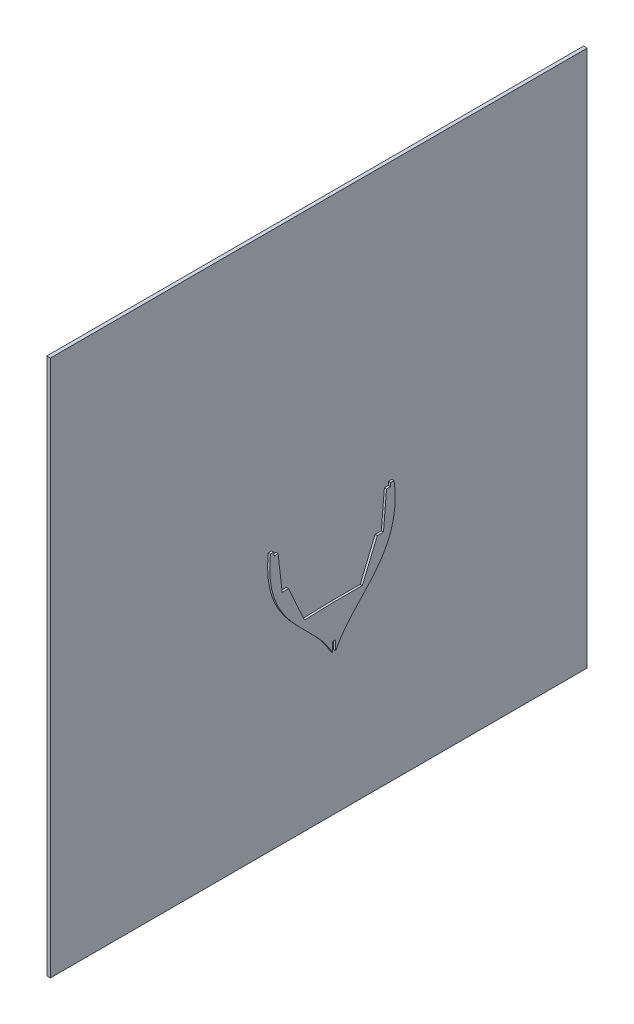
SolidWorks part; units mm, degrees
ref_plane "Plan de face" through (0, 0, 0) normal (0, 0, 1) x (1, 0, 0)
ref_plane "Plan de dessus" through (0, 0, 0) normal (0, 1, 0) x (1, 0, 0)
ref_plane "Plan de droite" through (0, 0, 0) normal (1, 0, 0) x (0, 0, -1)
sketch "Esquisse1" plane through (0, 0, 0) normal (0, 0, 1) x (1, 0, 0)
  point P0 (-20, 0)
  dimension "D1" = 20
sketch3d "Esquisse3D1"
  line L1 (-20, 1121.2893, 777.275) -> (-20, 1121.2893, -722.725)
  line L2 (-20, 1121.2893, 777.275) -> (-20, -378.7107, 777.275)
  line L3 (-20, -378.7107, 777.275) -> (-20, -378.7107, -722.725)
  line L4 (-20, 1121.2893, -722.725) -> (-20, -378.7107, -722.725)
  dimension "D1" = 1500
  dimension "D2" = 1500
extrude "Boss.-Extru.2" add sketch "Esquisse3D1" along direction (1, 0, 0) on the side of the normal blind 10 contours L2 L1 L4 L3
sketch "Esquisse2" plane through (0, 0, 0) normal (1, 0, 0) x (0, 0, -1)
  line L0 (0, 0) -> (-6.8072, 424.8009) construction
  line L1 (167.0671, 360.8778) -> (192.8736, 170.8481) construction
  line L2 (192.8736, 170.8481) -> (45.1534, 132.004) construction
  line L3 (45.1534, 132.004) -> (-0.3336, 20.8172) construction
  line L4 (167.0671, 360.8778) -> (157.0671, 360.8778)
  line L5 (157.0671, 360.8778) -> (157.0671, 350.8778)
  line L6 (157.0671, 350.8778) -> (145.964, 350.8778)
  line L7 (145.964, 350.8778) -> (137.4829, 250.8778)
  line L8 (137.4829, 250.8778) -> (120.1518, 250.8778)
  line L9 (120.1518, 250.8778) -> (78.3945, 150.8778)
  line L10 (78.3945, 150.8778) -> (-2.4177, 150.8778)
  line L15 (-178.5441, 355.3396) -> (-198.2487, 164.5806) construction
  line L16 (-198.2487, 164.5806) -> (-49.3597, 130.4895) construction
  line L17 (-49.3597, 130.4895) -> (-0.3336, 20.8172) construction
  line L18 (-83.1885, 148.2885) -> (-2.4177, 150.8778)
  line L19 (-128.1284, 246.8993) -> (-83.1885, 148.2885)
  line L20 (-145.4506, 246.344) -> (-128.1284, 246.8993)
  line L21 (-157.1314, 346.0209) -> (-145.4506, 246.344)
  line L22 (-168.2288, 345.6651) -> (-157.1314, 346.0209)
  line L23 (-168.5493, 355.66) -> (-168.2288, 345.6651)
  line L24 (-178.5441, 355.3396) -> (-168.5493, 355.66)
  spline S0 degree 3 poles (167.0671, 360.8778) (192.8736, 170.8481) (45.1534, 132.004) (-0.3336, 20.8172) knots 0 0 0 0 1 1 1 1
  spline S1 degree 3 poles (-178.5441, 355.3396) (-198.2487, 164.5806) (-49.3597, 130.4895) (-0.3336, 20.8172) knots 0 0 0 0 1 1 1 1
  point P7 (148.914, 349.4847)
  point P15 (137.4829, 249.1859)
  point P16 (145.964, 349.4847)
  point P17 (120.1518, 249.5547)
  point P18 (78.3945, 150.8778)
  dimension "D1" = 10
  dimension "D2" = 10
  dimension "D3" = 100
  dimension "D4" = 100
extrude "Boss.-Extru.3" add sketch "Esquisse2" along normal blind 6 separate body
sketch "Esquisse3" plane through (6, 0, 0) normal (1, 0, 0) x (0, 0, -1)
  line L0 (-5.0251, 30.5222) -> (-5.0251, 57.5222)
  line L1 (-5.0251, 57.5222) -> (3.9749, 57.5222)
  line L2 (3.9749, 57.5222) -> (3.9749, 30.5222)
  line L3 (-5.0251, 30.5222) -> (-13.4562, 12.9213)
  line L4 (-13.4562, 12.9213) -> (17.9304, 10.6418)
  line L5 (17.9304, 10.6418) -> (3.9749, 30.5222)
  spline S0 degree 3 poles (-178.5441, 355.3396) (-198.2487, 164.5806) (-49.3597, 130.4895) (-0.3336, 20.8172) knots 0 0 0 0 1 1 1 1 construction
  spline S1 degree 3 poles (-0.3336, 20.8172) (45.1534, 132.004) (192.8736, 170.8481) (167.0671, 360.8778) knots 0 0 0 0 1 1 1 1 construction
  dimension "D1" = 9
  dimension "D2" = 27
extrude "Enlèv. mat.-Extru.1" cut sketch "Esquisse3" against normal blind 6
